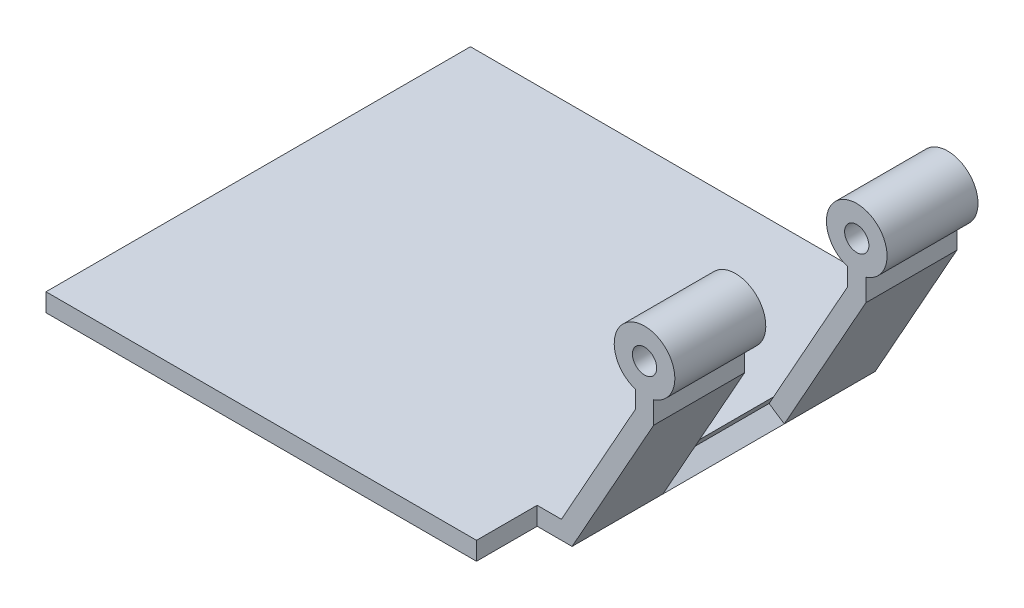
SolidWorks part; units mm, degrees
ref_plane "Front Plane" through (0, 0, 0) normal (0, 0, 1) x (1, 0, 0)
ref_plane "Top Plane" through (0, 0, 0) normal (0, 1, 0) x (1, 0, 0)
ref_plane "Right Plane" through (0, 0, 0) normal (1, 0, 0) x (0, 0, -1)
sketch "Sketch1" plane through (0, 0, 0) normal (0, 0, 1) x (1, 0, 0)
  line L0 (0, 3) -> (0, 0)
  line L1 (0, 0) -> (81.7588, 0)
  line L4 (92.2108, 24.8151) -> (80, 3)
  line L5 (80, 3) -> (0, 3)
  line L9 (81.7588, 0) -> (95.2108, 24.0326)
  line L11 (92.2108, 24.8151) -> (92.2108, 29.8151)
  line L12 (95.2108, 24.0326) -> (95.2108, 29.8151)
  line L13 (93.7108, 38.7108) -> (93.7108, 13.1897) construction
  line L14 (92.2108, 29.8151) -> (95.2108, 29.8151)
  circle A0 centre (93.7108, 32.4609) radius 5
  dimension "D9" = 10
  dimension "D1" = 80
  dimension "D2" = 3
  dimension "D3" = 25
  dimension "D4" = 3
  dimension "D5" = 119.237
  dimension "D6" = 5
  dimension "D7" = 3
  dimension "D8" = 1.5
extrude "Boss-Extrude1" add sketch "Sketch1" along normal blind 50 contours L9 L12 L14 L11 L4 L5 L0 L1 | A0
sketch "Sketch2" plane through (0, 0, 0) normal (0, 0, 1) x (1, 0, 0)
  circle A1 centre (93.7108, 32.4609) radius 2
  arc A2 (95.2108, 27.6912) -> (92.2108, 27.6912) centre (93.7108, 32.4609) ccw construction
  point P2 (88.697, 32.4609)
  point P11 (98.7108, 32.4609)
  point P12 (89.1184, 32.4609)
  point P13 (0, 0)
  point P14 (88.697, 32.4609)
  point P15 (88.697, 32.4609)
  dimension "D3" = 4
extrude "Cut-Extrude1" cut sketch "Sketch2" along normal through all
sketch "Sketch7" plane through (62.2541, -34.846, 0) normal (0.8726, -0.4884, 0) x (0, 0, -1)
  line L0 (-35, 89.9022) -> (-35, 28.0637) construction
  line L1 (-15, 89.9022) -> (-15, 25.2431) construction
  line L2 (-50, 39.9334) -> (-50, 67.4747) construction
  line L3 (0, 39.9334) -> (0, 67.4747) construction
  line L4 (-50, 39.9334) -> (0, 39.9334) construction
  line L5 (-35, 79.9206) -> (-15, 79.9206)
  line L6 (-35, 79.9206) -> (-35, 39.9334)
  line L7 (-35, 39.9334) -> (-15, 39.9334)
  line L8 (-15, 79.9206) -> (-15, 39.9334)
  point P6 (-35, 58.9829)
  dimension "D1" = 15
  dimension "D2" = 15
extrude "Cut-Extrude3" cut sketch "Sketch7" against normal blind 10 and the other way blind 10
sketch "Sketch8" plane through (0, 0, 0) normal (0, 0, 1) x (1, 0, 0)
  line L0 (66.951, 3) -> (66.951, 0)
  line L1 (80, 3) -> (0, 3) construction
  line L2 (0, 0) -> (81.7588, 0) construction
  line L3 (66.951, 0) -> (81.7588, 0)
  line L4 (81.7588, 0) -> (79.254, 1.6672)
  line L5 (92.2108, 24.8151) -> (80, 3) construction
  line L6 (79.254, 1.6672) -> (80, 3)
  line L7 (80, 3) -> (66.951, 3)
extrude "Boss-Extrude2" add sketch "Sketch8" along normal through all
sketch "Sketch9" plane through (0, 0, 0) normal (1, 0, 0) x (0, 0, -1)
  line L0 (-35, 27.6912) -> (-35, 37.4609) construction
  line L1 (-35, 37.4609) -> (-15, 37.4609)
  line L2 (-35, 37.4609) -> (-35, 26.5645)
  line L3 (-35, 26.5645) -> (-15, 26.5645)
  line L4 (-15, 37.4609) -> (-15, 26.5645)
  line L5 (-15, 24.0326) -> (-15, 27.6912) construction
extrude "Cut-Extrude4" cut sketch "Sketch9" along normal up to next
sketch "Sketch11" plane through (0, 0, 50) normal (0, 0, 1) x (1, 0, 0)
  line L0 (80, 3) -> (0, 3) construction
  line L1 (0, 0) -> (5, 0)
  line L2 (0, 0) -> (0, 3)
  line L3 (0, 3) -> (5, 3)
  line L4 (5, 0) -> (5, 3)
  point P7 (5, 1.5)
  dimension "D1" = 5
extrude "Cut-Extrude6" cut sketch "Sketch11" against normal up to body separate body
sketch "Sketch12" plane through (0, 3, 0) normal (0, 1, 0) x (1, 0, 0)
  line L0 (80, -15) -> (80, 0) construction
  line L1 (5, 10) -> (76, 10)
  line L2 (5, 10) -> (5, -60)
  line L3 (5, -60) -> (76, -60)
  line L4 (76, 10) -> (76, -60)
  line L5 (5, 0) -> (5, -50) construction
  line L6 (80, 0) -> (5, 0) construction
  line L7 (80, -50) -> (5, -50) construction
  dimension "D1" = 4
  dimension "D2" = 10
  dimension "D3" = 10
extrude "Boss-Extrude3" add sketch "Sketch12" against normal through all
